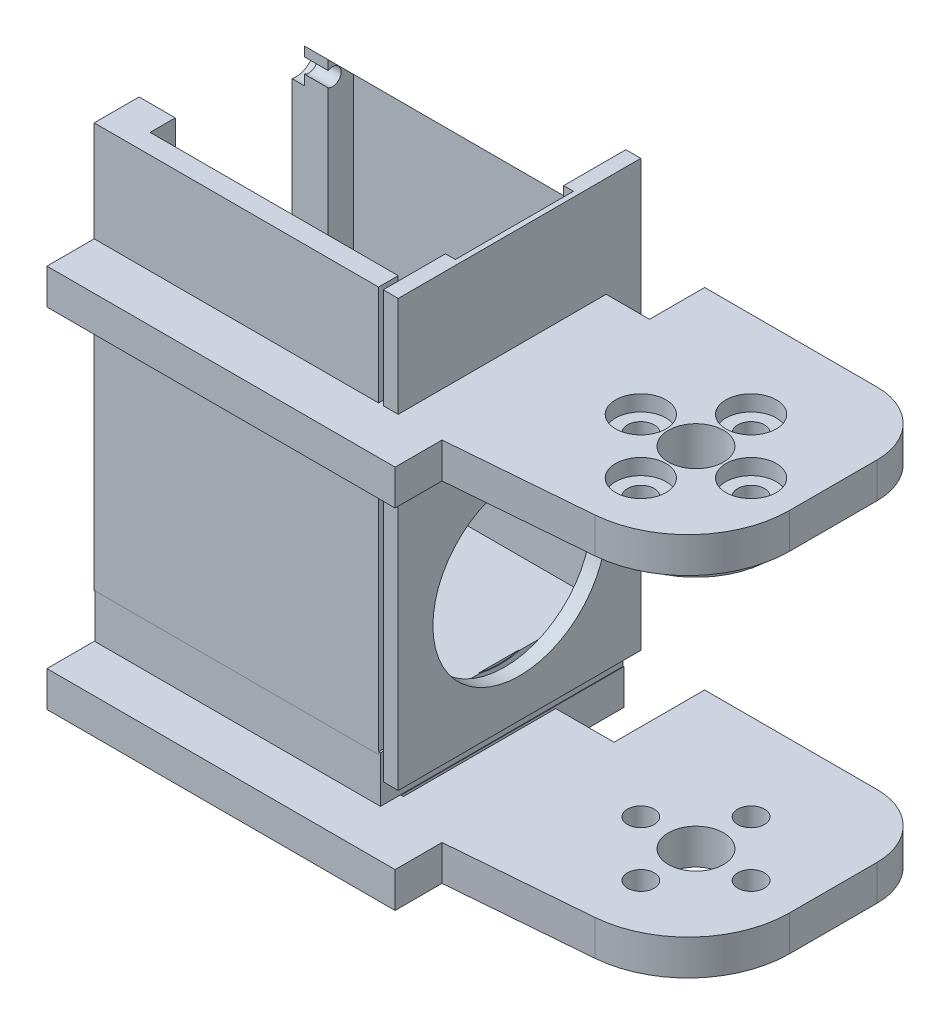
SolidWorks part; units mm, degrees
ref_plane "Front Plane" through (0, 0, 0) normal (0, 0, 1) x (1, 0, 0)
ref_plane "Top Plane" through (0, 0, 0) normal (0, 1, 0) x (1, 0, 0)
ref_plane "Right Plane" through (0, 0, 0) normal (1, 0, 0) x (0, 0, -1)
ref_plane "PY_m23_300" through (0, -23.3, 0) normal (0, 1, 0) x (1, 0, 0)
sketch "S_prism1" plane through (0, -23.3, 0) normal (0, 1, 0) x (1, 0, 0)
  line L0 (13, 10) -> (13, -1.1138)
  line L1 (1.1535, -13.9707) -> (-16.9, -15.45)
  line L2 (-16.9, -15.45) -> (-16.9, 18)
  line L3 (-16.9, 18) -> (5, 18)
  arc A0 (5, 18) -> (13, 10) centre (5.0002, 10.0002) cw
  arc A1 (13, -1.1138) -> (1.1535, -13.9707) centre (0.1, -1.1138) cw
extrude "Boss_1" add sketch "S_prism1" along normal blind 4.5
ref_plane "PY_p17_750" through (0, 17.75, 0) normal (0, 1, 0) x (1, 0, 0)
sketch "S_cyl2" plane through (0, 17.75, 0) normal (0, 1, 0) x (1, 0, 0)
  circle A0 centre (0, 0) radius 9.5
  dimension "D1_S_cyl2" = 19
extrude "Boss_2" add sketch "S_cyl2" along normal blind 3.2
ref_plane "PY_p20_950" through (0, 20.95, 0) normal (0, 1, 0) x (1, 0, 0)
sketch "S_prism3" plane through (0, 20.95, 0) normal (0, 1, 0) x (1, 0, 0)
  line L0 (13, 10) -> (13, -1.1138)
  line L1 (1.1535, -13.9707) -> (-16.9, -15.45)
  line L2 (-16.9, -15.45) -> (-16.9, 18)
  line L3 (-16.9, 18) -> (5, 18)
  arc A0 (5, 18) -> (13, 10) centre (5.0002, 10.0002) cw
  arc A1 (13, -1.1138) -> (1.1535, -13.9707) centre (0.1, -1.1138) cw
extrude "Boss_3" add sketch "S_prism3" along normal blind 4.5
sketch "S_prism4" plane through (0, -23.3, 0) normal (0, 1, 0) x (1, 0, 0)
  line L0 (-24.3, 6.5) -> (-16.8, 6.5)
  line L1 (-16.8, 6.5) -> (-16.8, -15.45)
  line L2 (-16.8, -15.45) -> (-24.3, -15.45)
  line L3 (-24.3, -15.45) -> (-24.3, 6.5)
extrude "Boss_4" add sketch "S_prism4" along normal blind 4.5
sketch "S_prism5" plane through (0, -23.3, 0) normal (0, 1, 0) x (1, 0, 0)
  line L0 (-61, -12.85) -> (-16.8, -12.85)
  line L1 (-16.8, -12.85) -> (-16.8, -21.4)
  line L2 (-16.8, -21.4) -> (-61, -21.4)
  line L3 (-61, -21.4) -> (-61, -12.85)
extrude "Boss_5" add sketch "S_prism5" along normal blind 4.5
sketch "S_prism6" plane through (0, -23.3, 0) normal (0, 1, 0) x (1, 0, 0)
  line L0 (-61, 15.45) -> (-24.6, 15.45)
  line L1 (-24.6, 15.45) -> (-24.6, -15.45)
  line L2 (-24.6, -15.45) -> (-61, -15.45)
  line L3 (-61, -15.45) -> (-61, 15.45)
extrude "Boss_6" add sketch "S_prism6" along normal blind 4.5
sketch "S_prism7" plane through (0, 20.95, 0) normal (0, 1, 0) x (1, 0, 0)
  line L0 (-24.3, 11) -> (-16.8, 11)
  line L1 (-16.8, 11) -> (-16.8, -15.45)
  line L2 (-16.8, -15.45) -> (-24.3, -15.45)
  line L3 (-24.3, -15.45) -> (-24.3, 11)
extrude "Boss_7" add sketch "S_prism7" along normal blind 4.5
sketch "S_prism8" plane through (0, 20.95, 0) normal (0, 1, 0) x (1, 0, 0)
  line L0 (-61, -12.85) -> (-16.8, -12.85)
  line L1 (-16.8, -12.85) -> (-16.8, -21.4)
  line L2 (-16.8, -21.4) -> (-61, -21.4)
  line L3 (-61, -21.4) -> (-61, -12.85)
extrude "Boss_8" add sketch "S_prism8" along normal blind 4.5
ref_plane "PZ_m15_400" through (0, 0, -15.4) normal (0, 0, 1) x (1, 0, 0)
sketch "S_box9" plane through (0, 0, -15.4) normal (0, 0, 1) x (1, 0, 0)
  line L0 (-61, -13.2) -> (-24.9, -13.2)
  line L1 (-24.9, -13.2) -> (-24.9, -10.7)
  line L2 (-24.9, -10.7) -> (-61, -10.7)
  line L3 (-61, -10.7) -> (-61, -13.2)
  dimension "P1" = 61
  dimension "P2" = 13.2
  dimension "P3" = 24.9
  dimension "P4" = 13.2
  dimension "P5" = 24.9
  dimension "P6" = 10.7
  dimension "P7" = 61
  dimension "P8" = 10.7
extrude "Boss_9" add sketch "S_box9" along normal blind 30.8
sketch "S_box10" plane through (0, 0, -15.4) normal (0, 0, 1) x (1, 0, 0)
  line L0 (-61, -13.2) -> (-24.9, -13.2)
  line L1 (-24.9, -13.2) -> (-24.9, 38.2)
  line L2 (-24.9, 38.2) -> (-61, 38.2)
  line L3 (-61, 38.2) -> (-61, -13.2)
  dimension "P1" = 61
  dimension "P2" = 13.2
  dimension "P3" = 24.9
  dimension "P4" = 13.2
  dimension "P5" = 24.9
  dimension "P6" = 38.2
  dimension "P7" = 61
  dimension "P8" = 38.2
extrude "Boss_10" add sketch "S_box10" along normal blind 2.5
ref_plane "PZ_p12_900" through (0, 0, 12.9) normal (0, 0, 1) x (1, 0, 0)
sketch "S_box11" plane through (0, 0, 12.9) normal (0, 0, 1) x (1, 0, 0)
  line L0 (-61, -13.2) -> (-24.9, -13.2)
  line L1 (-24.9, -13.2) -> (-24.9, 38.2)
  line L2 (-24.9, 38.2) -> (-61, 38.2)
  line L3 (-61, 38.2) -> (-61, -13.2)
  dimension "P1" = 61
  dimension "P2" = 13.2
  dimension "P3" = 24.9
  dimension "P4" = 13.2
  dimension "P5" = 24.9
  dimension "P6" = 38.2
  dimension "P7" = 61
  dimension "P8" = 38.2
extrude "Boss_11" add sketch "S_box11" along normal blind 2.5
sketch "S_box12" plane through (0, 0, -15.4) normal (0, 0, 1) x (1, 0, 0)
  line L0 (-61, -13.2) -> (-56.4, -13.2)
  line L1 (-56.4, -13.2) -> (-56.4, 38.2)
  line L2 (-56.4, 38.2) -> (-61, 38.2)
  line L3 (-61, 38.2) -> (-61, -13.2)
  dimension "P1" = 61
  dimension "P2" = 13.2
  dimension "P3" = 56.4
  dimension "P4" = 13.2
  dimension "P5" = 56.4
  dimension "P6" = 38.2
  dimension "P7" = 61
  dimension "P8" = 38.2
extrude "Boss_12" add sketch "S_box12" along normal blind 30.8
sketch "S_box13" plane through (0, 0, -15.4) normal (0, 0, 1) x (1, 0, 0)
  line L0 (-24.3, -15.9) -> (-22.4, -15.9)
  line L1 (-22.4, -15.9) -> (-22.4, 38.2)
  line L2 (-22.4, 38.2) -> (-24.3, 38.2)
  line L3 (-24.3, 38.2) -> (-24.3, -15.9)
  dimension "P1" = 24.3
  dimension "P2" = 15.9
  dimension "P3" = 22.4
  dimension "P4" = 15.9
  dimension "P5" = 22.4
  dimension "P6" = 38.2
  dimension "P7" = 24.3
  dimension "P8" = 38.2
extrude "Boss_13" add sketch "S_box13" along normal blind 30.8
ref_plane "PZ_m15_380" through (0, 0, -15.38) normal (0, 0, 1) x (1, 0, 0)
sketch "S_box14" plane through (0, 0, -15.38) normal (0, 0, 1) x (1, 0, 0)
  line L0 (-60.93, -18.9) -> (-24.67, -18.9)
  line L1 (-24.67, -18.9) -> (-24.67, -12.9)
  line L2 (-24.67, -12.9) -> (-60.93, -12.9)
  line L3 (-60.93, -12.9) -> (-60.93, -18.9)
  dimension "P1" = 60.93
  dimension "P2" = 18.9
  dimension "P3" = 24.67
  dimension "P4" = 18.9
  dimension "P5" = 24.67
  dimension "P6" = 12.9
  dimension "P7" = 60.93
  dimension "P8" = 12.9
extrude "Boss_14" add sketch "S_box14" along normal blind 30.76
ref_plane "PY_m23_400" through (0, -23.4, 0) normal (0, 1, 0) x (1, 0, 0)
sketch "S_hole15" plane through (0, -23.4, 0) normal (0, 1, 0) x (1, 0, 0)
  circle A0 centre (0, 0) radius 3.5
  dimension "D1_S_hole15" = 7
extrude "Hole_15" cut sketch "S_hole15" along normal blind 4.7
sketch "S_hole16" plane through (0, -23.4, 0) normal (0, 1, 0) x (1, 0, 0)
  circle A0 centre (7, 0) radius 1.7
  dimension "D1_S_hole16" = 3.4
  dimension "P2" = 7
extrude "Hole_16" cut sketch "S_hole16" along normal blind 4.7
sketch "S_hole17" plane through (0, -23.4, 0) normal (0, 1, 0) x (1, 0, 0)
  circle A0 centre (0, -7) radius 1.7
  dimension "D1_S_hole17" = 3.4
  dimension "P2" = 7
extrude "Hole_17" cut sketch "S_hole17" along normal blind 4.7
sketch "S_hole18" plane through (0, -23.4, 0) normal (0, 1, 0) x (1, 0, 0)
  circle A0 centre (-7, 0) radius 1.7
  dimension "D1_S_hole18" = 3.4
  dimension "P2" = 7
extrude "Hole_18" cut sketch "S_hole18" along normal blind 4.7
sketch "S_hole19" plane through (0, -23.4, 0) normal (0, 1, 0) x (1, 0, 0)
  circle A0 centre (0, 7) radius 1.7
  dimension "D1_S_hole19" = 3.4
  dimension "P2" = 7
extrude "Hole_19" cut sketch "S_hole19" along normal blind 4.7
sketch "S_hole20" plane through (0, -23.4, 0) normal (0, 1, 0) x (1, 0, 0)
  circle A0 centre (7, 0) radius 3.2
  dimension "D1_S_hole20" = 6.4
  dimension "P2" = 7
extrude "Hole_20" cut sketch "S_hole20" along normal blind 1.6
sketch "S_hole21" plane through (0, -23.4, 0) normal (0, 1, 0) x (1, 0, 0)
  circle A0 centre (0, -7) radius 3.2
  dimension "D1_S_hole21" = 6.4
  dimension "P2" = 7
extrude "Hole_21" cut sketch "S_hole21" along normal blind 1.6
sketch "S_hole22" plane through (0, -23.4, 0) normal (0, 1, 0) x (1, 0, 0)
  circle A0 centre (-7, 0) radius 3.2
  dimension "D1_S_hole22" = 6.4
  dimension "P2" = 7
extrude "Hole_22" cut sketch "S_hole22" along normal blind 1.6
sketch "S_hole23" plane through (0, -23.4, 0) normal (0, 1, 0) x (1, 0, 0)
  circle A0 centre (0, 7) radius 3.2
  dimension "D1_S_hole23" = 6.4
  dimension "P2" = 7
extrude "Hole_23" cut sketch "S_hole23" along normal blind 1.6
ref_plane "PY_p17_650" through (0, 17.65, 0) normal (0, 1, 0) x (1, 0, 0)
sketch "S_hole24" plane through (0, 17.65, 0) normal (0, 1, 0) x (1, 0, 0)
  circle A0 centre (0, 0) radius 3.5
  dimension "D1_S_hole24" = 7
extrude "Hole_24" cut sketch "S_hole24" along normal blind 7.9
sketch "S_hole25" plane through (0, 17.65, 0) normal (0, 1, 0) x (1, 0, 0)
  circle A0 centre (7, 0) radius 1.7
  dimension "D1_S_hole25" = 3.4
  dimension "P2" = 7
extrude "Hole_25" cut sketch "S_hole25" along normal blind 7.9
sketch "S_hole26" plane through (0, 17.65, 0) normal (0, 1, 0) x (1, 0, 0)
  circle A0 centre (0, -7) radius 1.7
  dimension "D1_S_hole26" = 3.4
  dimension "P2" = 7
extrude "Hole_26" cut sketch "S_hole26" along normal blind 7.9
sketch "S_hole27" plane through (0, 17.65, 0) normal (0, 1, 0) x (1, 0, 0)
  circle A0 centre (-7, 0) radius 1.7
  dimension "D1_S_hole27" = 3.4
  dimension "P2" = 7
extrude "Hole_27" cut sketch "S_hole27" along normal blind 7.9
sketch "S_hole28" plane through (0, 17.65, 0) normal (0, 1, 0) x (1, 0, 0)
  circle A0 centre (0, 7) radius 1.7
  dimension "D1_S_hole28" = 3.4
  dimension "P2" = 7
extrude "Hole_28" cut sketch "S_hole28" along normal blind 7.9
ref_plane "PY_p23_450" through (0, 23.45, 0) normal (0, 1, 0) x (1, 0, 0)
sketch "S_hole29" plane through (0, 23.45, 0) normal (0, 1, 0) x (1, 0, 0)
  circle A0 centre (7, 0) radius 3.2
  dimension "D1_S_hole29" = 6.4
  dimension "P2" = 7
extrude "Hole_29" cut sketch "S_hole29" along normal blind 2.1
sketch "S_hole30" plane through (0, 23.45, 0) normal (0, 1, 0) x (1, 0, 0)
  circle A0 centre (0, -7) radius 3.2
  dimension "D1_S_hole30" = 6.4
  dimension "P2" = 7
extrude "Hole_30" cut sketch "S_hole30" along normal blind 2.1
sketch "S_hole31" plane through (0, 23.45, 0) normal (0, 1, 0) x (1, 0, 0)
  circle A0 centre (-7, 0) radius 3.2
  dimension "D1_S_hole31" = 6.4
  dimension "P2" = 7
extrude "Hole_31" cut sketch "S_hole31" along normal blind 2.1
sketch "S_hole32" plane through (0, 23.45, 0) normal (0, 1, 0) x (1, 0, 0)
  circle A0 centre (0, 7) radius 3.2
  dimension "D1_S_hole32" = 6.4
  dimension "P2" = 7
extrude "Hole_32" cut sketch "S_hole32" along normal blind 2.1
sketch "S_cut33" plane through (0, 0, 0) normal (0, 0, 1) x (1, 0, 0)
  line L0 (-3.4, 17.65) -> (3.4, 17.65)
  line L1 (3.4, 17.65) -> (3.4, 18.65)
  line L2 (3.4, 18.65) -> (-3.4, 18.65)
  line L3 (-3.4, 18.65) -> (-3.4, 17.65)
  dimension "P1" = 3.4
  dimension "P2" = 17.65
  dimension "P3" = 3.4
  dimension "P4" = 17.65
  dimension "P5" = 3.4
  dimension "P6" = 18.65
  dimension "P7" = 3.4
  dimension "P8" = 18.65
extrude "Pocket_33" cut sketch "S_cut33" along normal blind 10
ref_plane "PX_m61_100" through (-61.1, 0, 0) normal (1, 0, 0) x (0, 0, -1)
sketch "S_hole34" plane through (-61.1, 0, 0) normal (1, 0, 0) x (0, 0, -1)
  circle A0 centre (0, 0) radius 10.5
  dimension "D1_S_hole34" = 21
extrude "Hole_34" cut sketch "S_hole34" along normal blind 4.8
ref_plane "PZ_m9_700" through (0, 0, -9.7) normal (0, 0, 1) x (1, 0, 0)
sketch "S_cut35" plane through (0, 0, -9.7) normal (0, 0, 1) x (1, 0, 0)
  line L0 (-61.1, 10.9) -> (-56.35, 10.9)
  line L1 (-56.35, 10.9) -> (-56.35, 30.4)
  line L2 (-56.35, 30.4) -> (-61.1, 30.4)
  line L3 (-61.1, 30.4) -> (-61.1, 10.9)
  dimension "P1" = 61.1
  dimension "P2" = 10.9
  dimension "P3" = 56.35
  dimension "P4" = 10.9
  dimension "P5" = 56.35
  dimension "P6" = 30.4
  dimension "P7" = 61.1
  dimension "P8" = 30.4
extrude "Pocket_35" cut sketch "S_cut35" along normal blind 19.4
sketch "S_cut36" plane through (0, 0, -9.7) normal (0, 0, 1) x (1, 0, 0)
  line L0 (-61.1, 30.4) -> (-56.35, 30.4)
  line L1 (-56.35, 30.4) -> (-56.35, 38.7)
  line L2 (-56.35, 38.7) -> (-61.1, 38.7)
  line L3 (-61.1, 38.7) -> (-61.1, 30.4)
  dimension "P1" = 61.1
  dimension "P2" = 30.4
  dimension "P3" = 56.35
  dimension "P4" = 30.4
  dimension "P5" = 56.35
  dimension "P6" = 38.7
  dimension "P7" = 61.1
  dimension "P8" = 38.7
extrude "Pocket_36" cut sketch "S_cut36" along normal blind 19.4
ref_plane "PZ_m3_500" through (0, 0, -3.5) normal (0, 0, 1) x (1, 0, 0)
sketch "S_cut37" plane through (0, 0, -3.5) normal (0, 0, 1) x (1, 0, 0)
  line L0 (-61.1, 0) -> (-56.35, 0)
  line L1 (-56.35, 0) -> (-56.35, 11)
  line L2 (-56.35, 11) -> (-61.1, 11)
  line L3 (-61.1, 11) -> (-61.1, 0)
  dimension "P1" = 61.1
  dimension "P2" = 56.35
  dimension "P3" = 56.35
  dimension "P4" = 11
  dimension "P5" = 61.1
  dimension "P6" = 11
extrude "Pocket_37" cut sketch "S_cut37" along normal blind 7
ref_plane "PZ_m15_900" through (0, 0, -15.9) normal (0, 0, 1) x (1, 0, 0)
sketch "S_cut38" plane through (0, 0, -15.9) normal (0, 0, 1) x (1, 0, 0)
  line L0 (-61.2, -10) -> (-58.3, -10)
  line L1 (-58.3, -10) -> (-58.3, 10)
  line L2 (-58.3, 10) -> (-61.2, 10)
  line L3 (-61.2, 10) -> (-61.2, -10)
  dimension "P1" = 61.2
  dimension "P2" = 10
  dimension "P3" = 58.3
  dimension "P4" = 10
  dimension "P5" = 58.3
  dimension "P6" = 10
  dimension "P7" = 61.2
  dimension "P8" = 10
extrude "Pocket_38" cut sketch "S_cut38" along normal blind 15.9
sketch "S_hole39" plane through (-61.1, 0, 0) normal (1, 0, 0) x (0, 0, -1)
  circle A0 centre (-10.25, 8.3) radius 1.1
  dimension "D1_S_hole39" = 2.2
  dimension "P2" = 10.25
  dimension "P3" = 8.3
extrude "Hole_39" cut sketch "S_hole39" along normal blind 4.8
sketch "S_hole40" plane through (-61.1, 0, 0) normal (1, 0, 0) x (0, 0, -1)
  circle A0 centre (-10.25, 8.3) radius 2.3
  dimension "D1_S_hole40" = 4.6
  dimension "P2" = 10.25
  dimension "P3" = 8.3
extrude "Hole_40" cut sketch "S_hole40" along normal blind 1.7
sketch "S_hole41" plane through (-61.1, 0, 0) normal (1, 0, 0) x (0, 0, -1)
  circle A0 centre (10.25, 32.75) radius 1.1
  dimension "D1_S_hole41" = 2.2
  dimension "P2" = 10.25
  dimension "P3" = 32.75
extrude "Hole_41" cut sketch "S_hole41" along normal blind 4.8
sketch "S_hole42" plane through (-61.1, 0, 0) normal (1, 0, 0) x (0, 0, -1)
  circle A0 centre (10.25, 32.75) radius 2.3
  dimension "D1_S_hole42" = 4.6
  dimension "P2" = 10.25
  dimension "P3" = 32.75
extrude "Hole_42" cut sketch "S_hole42" along normal blind 1.7
sketch "S_hole43" plane through (-61.1, 0, 0) normal (1, 0, 0) x (0, 0, -1)
  circle A0 centre (-10.25, 32.75) radius 1.1
  dimension "D1_S_hole43" = 2.2
  dimension "P2" = 10.25
  dimension "P3" = 32.75
extrude "Hole_43" cut sketch "S_hole43" along normal blind 4.8
sketch "S_hole44" plane through (-61.1, 0, 0) normal (1, 0, 0) x (0, 0, -1)
  circle A0 centre (-10.25, 32.75) radius 2.3
  dimension "D1_S_hole44" = 4.6
  dimension "P2" = 10.25
  dimension "P3" = 32.75
extrude "Hole_44" cut sketch "S_hole44" along normal blind 1.7
ref_plane "PX_m25_000" through (-25, 0, 0) normal (1, 0, 0) x (0, 0, -1)
sketch "S_hole45" plane through (-25, 0, 0) normal (1, 0, 0) x (0, 0, -1)
  circle A0 centre (0, 0) radius 11
  dimension "D1_S_hole45" = 22
extrude "Hole_45" cut sketch "S_hole45" along normal blind 2.7
ref_plane "PZ_m7_500" through (0, 0, -7.5) normal (0, 0, 1) x (1, 0, 0)
sketch "S_cut46" plane through (0, 0, -7.5) normal (0, 0, 1) x (1, 0, 0)
  line L0 (-24.9, 8.1) -> (-23.05, 8.1)
  line L1 (-23.05, 8.1) -> (-23.05, 38.7)
  line L2 (-23.05, 38.7) -> (-24.9, 38.7)
  line L3 (-24.9, 38.7) -> (-24.9, 8.1)
  dimension "P1" = 24.9
  dimension "P2" = 8.1
  dimension "P3" = 23.05
  dimension "P4" = 8.1
  dimension "P5" = 23.05
  dimension "P6" = 38.7
  dimension "P7" = 24.9
  dimension "P8" = 38.7
extrude "Pocket_46" cut sketch "S_cut46" along normal blind 15
sketch "S_pcut47" plane through (-61.1, 0, 0) normal (1, 0, 0) x (0, 0, -1)
  line L0 (16, 38.8) -> (16, 28.6)
  line L1 (16, 28.6) -> (5.8, 38.8)
  line L2 (5.8, 38.8) -> (16, 38.8)
extrude "Cut_47" cut sketch "S_pcut47" along normal blind 36.3
equation "\"plate_t\" = 3"
equation "\"clearance\" = 0.5"
